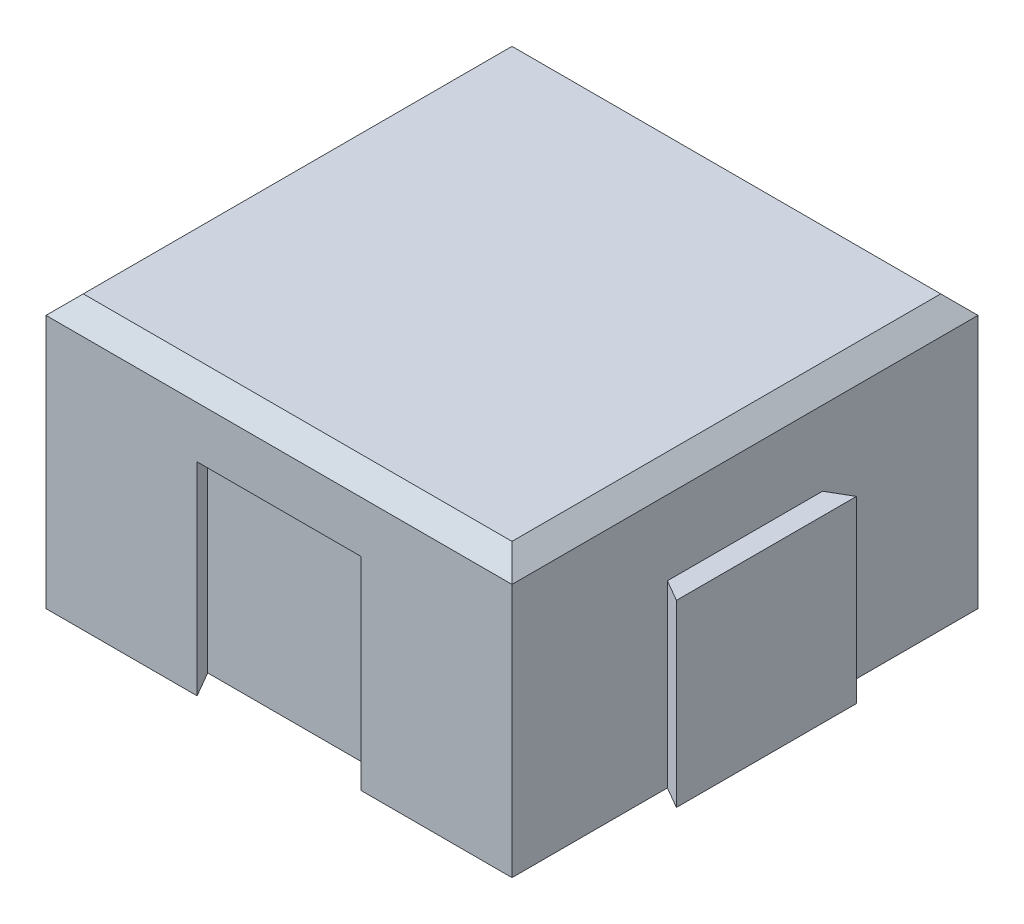
SolidWorks part; units mm, degrees
ref_plane "Left Plane" through (0, 0, 0) normal (0, 0, 1) x (1, 0, 0)
ref_plane "Bottom Plane" through (0, 0, 0) normal (0, 1, 0) x (1, 0, 0)
ref_plane "Back Plane" through (0, 0, 0) normal (1, 0, 0) x (0, 0, -1)
sketch "Sketch1" plane through (0, 0, 0) normal (0, 1, 0) x (1, 0, 0)
  line L1 (0, 0) -> (50, 0)
  line L2 (0, 0) -> (0, 50)
  line L3 (0, 50) -> (50, 50)
  line L4 (50, 0) -> (50, 50)
  dimension "D1" = 50
extrude "Boss-Extrude1" add sketch "Sketch1" along normal blind 30
sketch "Sketch3" plane through (0, 0, 0) normal (0, 1, 0) x (1, 0, 0)
  line L0 (50, 33.5566) -> (52.5, 35) construction
  line L1 (50, 0) -> (50, 50) construction
  line L2 (52.5, 35) -> (52.5, 15) construction
  line L3 (52.5, 15) -> (50, 16.4434) construction
  line L4 (50, 25) -> (52.5, 25) construction
  line L5 (16.4434, 50) -> (15, 52.5) construction
  line L6 (50, 50) -> (0, 50) construction
  line L7 (15, 52.5) -> (35, 52.5) construction
  line L8 (35, 52.5) -> (33.5566, 50) construction
  line L9 (25, 52.5) -> (25, 50) construction
  line L10 (0, 33.5566) -> (2.5, 35) construction
  line L11 (0, 50) -> (0, 0) construction
  line L12 (2.5, 35) -> (2.5, 15) construction
  line L13 (2.5, 15) -> (0, 16.4434) construction
  line L14 (0, 25) -> (2.5, 25) construction
  line L15 (16.4434, 0) -> (15, 2.5) construction
  line L16 (0, 0) -> (50, 0) construction
  line L17 (15, 2.5) -> (35, 2.5) construction
  line L18 (35, 2.5) -> (33.5566, 0) construction
  line L19 (25, 0) -> (25, 2.5) construction
  line L20 (50, 16.6743) -> (50, 33.3257)
  line L21 (33.3257, 50) -> (16.6743, 50)
  line L23 (16.4434, 0) -> (33.5566, 0) construction
  line L24 (50, 33.3257) -> (52.3, 34.6536)
  line L25 (52.3, 34.6536) -> (52.3, 15.3464)
  line L26 (52.3, 15.3464) -> (50, 16.6743)
  line L27 (52.3, 34.6536) -> (52.2, 34.8268) construction
  line L28 (16.2124, 0) -> (14.6536, 2.7)
  line L29 (52.3, 34.6536) -> (52.5, 34.6536) construction
  line L30 (14.6536, 2.7) -> (35.3464, 2.7)
  line L31 (35.3464, 2.7) -> (33.7876, 0)
  line L32 (33.7876, 0) -> (16.2124, 0)
  line L33 (35, 2.5) -> (35, 2.7) construction
  line L34 (35, 2.5) -> (35.1732, 2.4) construction
  line L35 (0, 33.7876) -> (2.7, 35.3464)
  line L36 (2.7, 35.3464) -> (2.7, 14.6536)
  line L37 (2.7, 14.6536) -> (0, 16.2124)
  line L38 (0, 16.2124) -> (0, 33.7876)
  line L39 (2.4, 14.8268) -> (2.5, 15) construction
  line L40 (2.5, 15) -> (2.7, 15) construction
  line L41 (16.6743, 50) -> (15.3464, 52.3)
  line L42 (15.3464, 52.3) -> (34.6536, 52.3)
  line L43 (34.6536, 52.3) -> (33.3257, 50)
  line L44 (15.3464, 52.5) -> (15.3464, 52.3) construction
  line L45 (15.1732, 52.2) -> (15.3464, 52.3) construction
  point P8 (50, 25)
  point P39 (52.3, 25)
  point P40 (25, 0)
  point P53 (0, 25)
  point P59 (25, 52.3)
  point P63 (25, 50)
  dimension "D1" = 0.2
  dimension "D2" = 60
  dimension "D3" = 2.5
  dimension "D4" = 20
extrude "Boss-Extrude2" add sketch "Sketch3" along normal blind 20 contours L20 L24 L25 L26
extrude "Boss-Extrude3" add sketch "Sketch3<3>" along normal blind 20 contours L21 L41 L42 L43
sketch "Sketch3<3>" plane through (0, 0, 0) normal (0, 1, 0) x (1, 0, 0) same geometry as "Sketch3"
extrude "Cut-Extrude5" cut sketch "Sketch3<6>" along normal blind 20 contours L38 L35 L36 L37
sketch "Sketch3<6>" plane through (0, 0, 0) normal (0, 1, 0) x (1, 0, 0) same geometry as "Sketch3"
extrude "Cut-Extrude6" cut sketch "Sketch3<7>" along normal blind 20 contours L32 L28 L30 L31
sketch "Sketch3<7>" plane through (0, 0, 0) normal (0, 1, 0) x (1, 0, 0) same geometry as "Sketch3"
chamfer "Chamfer1" distance 2 angle 45 4 edges at (25, 30, -50) (50, 30, -25) (25, 30, 0) (0, 30, -25)
sketch "Sketch4" plane through (0, 0, 0) normal (0, 1, 0) x (1, 0, 0)
  line L0 (12.5, 12.5) -> (37.5, 37.5) construction
  line L1 (12.5, 12.5) -> (37.5, 12.5) construction
  line L2 (12.5, 12.5) -> (12.5, 37.5) construction
  line L3 (12.5, 37.5) -> (37.5, 37.5) construction
  line L4 (37.5, 12.5) -> (37.5, 37.5) construction
  line L5 (12.5, 37.5) -> (37.5, 12.5) construction
  line L6 (0, 0) -> (12.5, 12.5) construction
  line L7 (12.5, 37.5) -> (0, 50) construction
  line L8 (50, 50) -> (37.5, 37.5) construction
  line L9 (50, 0) -> (37.5, 12.5) construction
  line L10 (0, 25) -> (25, 25) construction
  circle A0 centre (12.5, 37.5) radius 3.1
  circle A1 centre (37.5, 37.5) radius 3.1
  circle A2 centre (37.5, 12.5) radius 3.1
  circle A3 centre (12.5, 12.5) radius 3.1
  point P15 (12.5, 25)
  dimension "D1" = 6.2
extrude "Cut-Extrude4" cut sketch "Sketch4" along normal blind 4
chamfer "Chamfer2" distance 1 angle 45 4 edges at (37.5, 4, -9.4) (12.5, 4, -9.4) (12.5, 4, -34.4) (37.5, 4, -34.4)
chamfer "Chamfer3" distance 0.75 angle 45 24 edges at (41.8938, 0, 0) (50, 0, -8.3372) (50, 0, -41.6628) (41.6628, 0, -50) (8.3372, 0, -50) (0, 0, -41.8938) (0, 0, -8.1062) (8.1062, 0, 0) (12.5, 0, -34.4) (37.5, 0, -34.4) (37.5, 0, -9.4) (12.5, 0, -9.4) (51.15, 0, -16.0104) (52.3, 0, -25) (51.15, 0, -33.9896) (33.9896, 0, -51.15) (25, 0, -52.3) (16.0104, 0, -51.15) (1.35, 0, -34.567) (2.7, 0, -25) (1.35, 0, -15.433) (15.433, 0, -1.35) (25, 0, -2.7) (34.567, 0, -1.35)
chamfer "Chamfer4" distance 2.5 angle 45 2 edges at (25, 20, 0) (0, 20, -25)
